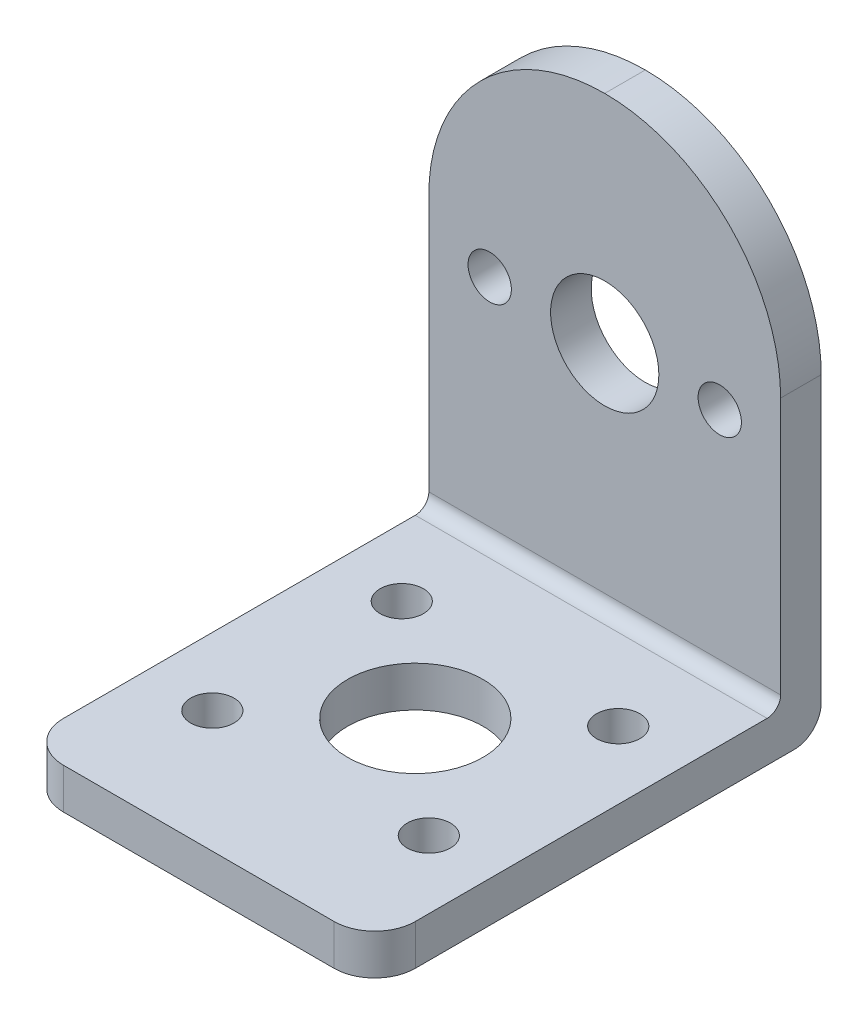
SolidWorks part; units mm, degrees
ref_plane "Front Plane" through (0, 0, 0) normal (0, 0, 1) x (1, 0, 0)
ref_plane "Top Plane" through (0, 0, 0) normal (0, 1, 0) x (1, 0, 0)
ref_plane "Right Plane" through (0, 0, 0) normal (1, 0, 0) x (0, 0, -1)
sketch "Sketch1" plane through (0, 0, 0) normal (0, 1, 0) x (1, 0, 0)
  line L0 (0, 16.5) -> (0, -16.5) construction
  line L1 (-13, 16.5) -> (13, 16.5)
  line L2 (-13, 16.5) -> (-13, -16.5)
  line L3 (-13, -16.5) -> (13, -16.5)
  line L4 (13, 16.5) -> (13, -16.5)
  line L5 (-13, 16.5) -> (13, -16.5) construction
  line L6 (-13, -16.5) -> (13, 16.5) construction
  line L7 (-13, -0.5) -> (13, -0.5) construction
  circle A0 centre (0, -0.5) radius 5
  circle A1 centre (8, 6.5) radius 1.6
  circle A2 centre (-8, 6.5) radius 1.6
  circle A3 centre (8, -7.5) radius 1.6
  circle A4 centre (-8, -7.5) radius 1.6
  point P0 (0, 0)
  point P14 (0, 0)
  dimension "D4" = 10
  dimension "D7" = 3.2
  dimension "D1" = 26
  dimension "D2" = 33
  dimension "D3" = 16
  dimension "D5" = 13
  dimension "D6" = 16
  dimension "D8" = 7
  dimension "D9" = 8
extrude "Boss-Extrude1" add sketch "Sketch1" along normal blind 3
fillet "Fillet2" radius 3 2 edges at (-13, 1.5, 16.5) (13, 1.5, 16.5)
sketch "Sketch2" plane through (0, 3, 0) normal (0, 1, 0) x (1, 0, 0)
  line L0 (13, -13.5) -> (13, 16.5) construction
  line L1 (-13, 16.5) -> (13, 16.5)
  line L2 (-13, 16.5) -> (-13, 13.5)
  line L3 (-13, 13.5) -> (13, 13.5)
  line L4 (13, 16.5) -> (13, 13.5)
  dimension "D1" = 3
extrude "Boss-Extrude2" add sketch "Sketch2" along normal blind 33
fillet "Fillet3" radius 13 2 edges at (-13, 36, -15) (13, 36, -15)
sketch "Sketch3" plane through (0, 0, -13.5) normal (0, 0, 1) x (1, 0, 0)
  line L0 (-10, 0) -> (10, 0) construction
  line L1 (13, 23) -> (13, 3) construction
  line L2 (0, 36) -> (0, 3) construction
  line L3 (-10, 3) -> (10, 3) construction
  line L4 (0, 20) -> (13, 20) construction
  circle A0 centre (0, 20) radius 4
  circle A1 centre (8.5, 20) radius 1.6
  circle A2 centre (-8.5, 20) radius 1.6
  dimension "D1" = 8
  dimension "D4" = 3.2
  dimension "D2" = 20
  dimension "D3" = 13
  dimension "D5" = 8.5
extrude "Cut-Extrude1" cut sketch "Sketch3" against normal blind 3
fillet "Fillet4" radius 2 1 edges at (0, 0, -16.5)
fillet "Fillet5" radius 1 1 edges at (0, 3, -13.5)
